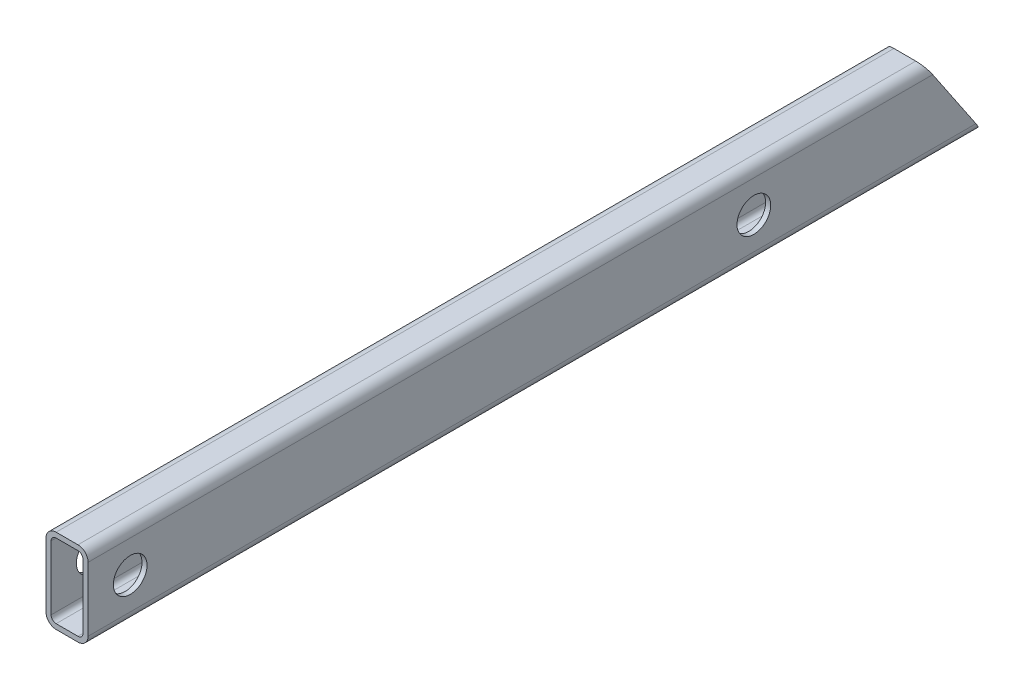
SolidWorks part; units mm, degrees
note: The reader was unsure of these and kept them because the rebuilt part matched: shared geometry of "Sketch2<6>".
material "AISI 1020 Steel, Cold Rolled"
ref_plane "Front Plane" through (0, 0, 0) normal (0, 0, 1) x (1, 0, 0)
ref_plane "Top Plane" through (0, 0, 0) normal (0, 1, 0) x (1, 0, 0)
ref_plane "Right Plane" through (0, 0, 0) normal (1, 0, 0) x (0, 0, -1)
sketch "Sketch1" plane through (0, 0, 0) normal (0, 0, 1) x (1, 0, 0)
  line L4 (0, 44) -> (0, 6)
  line L10 (3, 44) -> (3, 6)
  line L11 (6, 47) -> (18.9612, 47)
  line L12 (21.9612, 44) -> (21.9612, 6)
  line L13 (24.9612, 44) -> (24.9612, 6)
  line L14 (6, 50) -> (18.9612, 50)
  line L15 (6, 3) -> (18.9612, 3)
  line L16 (6, 0) -> (18.9612, 0)
  arc A0 (6, 3) -> (3, 6) centre (6, 6) cw
  arc A1 (6, 0) -> (0, 6) centre (6, 6) cw
  arc A2 (18.9612, 3) -> (21.9612, 6) centre (18.9612, 6) ccw
  arc A3 (18.9612, 0) -> (24.9612, 6) centre (18.9612, 6) ccw
  arc A4 (6, 47) -> (3, 44) centre (6, 44) ccw
  arc A5 (6, 50) -> (0, 44) centre (6, 44) ccw
  arc A6 (18.9612, 47) -> (21.9612, 44) centre (18.9612, 44) cw
  arc A7 (18.9612, 50) -> (24.9612, 44) centre (18.9612, 44) cw
extrude "Boss-Extrude1" add sketch "Sketch1" along normal blind 530.8
sketch "Sketch2" plane through (24.9612, 0, 0) normal (1, 0, 0) x (0, 0, -1)
  line L0 (-505.8, 25) -> (-135.8, 25)
  line L1 (-530.8, 6) -> (-530.8, 44) construction
  line L2 (-530.8, 25) -> (-530.8, 0)
  line L3 (-530.8, 0) -> (0, 0)
  line L4 (-530.8, 25) -> (-530.8, 50)
  line L5 (-530.8, 50) -> (-33.73, 50)
  line L6 (-33.73, 50) -> (0, 0)
  line L7 (0, 0) -> (0, 50)
  line L8 (0, 50) -> (-33.73, 50)
  circle A0 centre (-505.8, 25) radius 10
  circle A6 centre (-135.8, 25) radius 10
extrude "Cut-Extrude1" cut sketch "Sketch2" against normal through all
extrude "Cut-Extrude2" cut sketch "Sketch2<6>" against normal through all
sketch "Sketch2<6>" plane through (24.9612, 0, 0) normal (1, 0, 0) x (0, 0, -1) same geometry as "Sketch2"
sketch "Sketch3" plane through (24.9612, 0, 0) normal (1, 0, 0) x (0, 0, -1)
  line L0 (-16.865, 25) -> (0, 0)
  line L1 (-29.6824, 44) -> (-4.0476, 6) construction
  line L2 (0, 0) -> (-10, 0)
  line L3 (-16.865, 25) -> (-37.1165, 55.02)
  line L4 (-37.1165, 55.02) -> (-47.1165, 55.02)
  line L5 (-47.1165, 55.02) -> (-10, 0)
  line L6 (-16.865, 25) -> (-26.865, 25)
  line L7 (-26.865, 25) -> (-66.865, 25)
  circle A1 centre (-66.865, 25) radius 10
extrude "Cut-Extrude3" [suppressed] cut sketch "Sketch3" against normal through all
sketch "Sketch4" plane through (24.9612, 0, 0) normal (1, 0, 0) x (0, 0, -1)
  line L0 (-505.8, 25) -> (-555.8, 25)
  line L1 (-505.8, 25) -> (-505.8, 75)
  line L2 (-135.8, 25) -> (-135.8, 75)
  line L3 (-135.8, 25) -> (-85.8, 25)
  line L4 (-16.865, 25) -> (33.135, 25)
  line L5 (-29.6824, 44) -> (-4.0476, 6) construction
  line L6 (-16.865, 25) -> (-16.865, 75)
  line L8 (-454.8, 25) -> (-413.8424, 53.6788)
  arc A0 (33.135, 50) -> (33.135, 0) centre (33.135, 25) cw
  arc A1 (-454.8, 50) -> (-454.8, 0) centre (-454.8, 25) ccw
